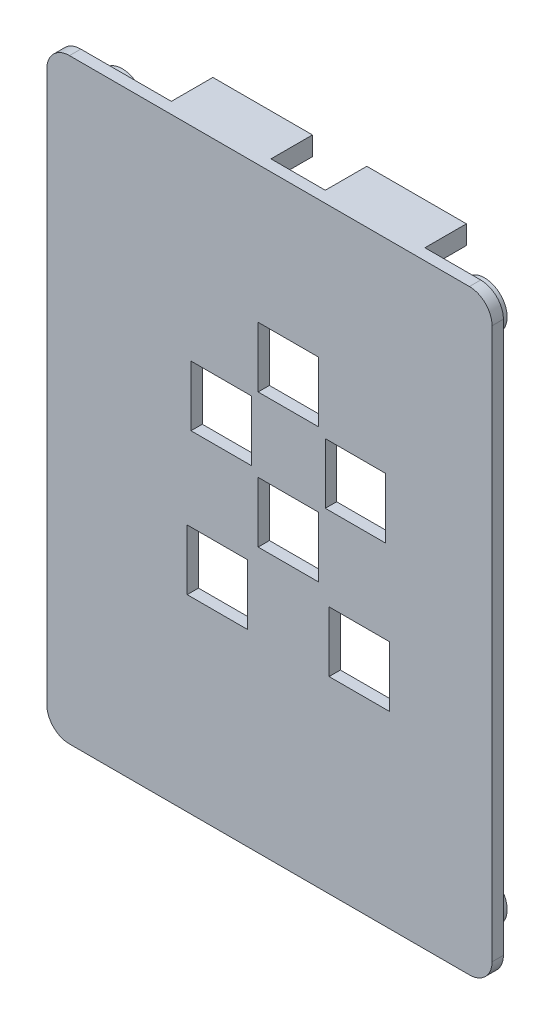
SolidWorks part; units mm, degrees
ref_plane "前视基准面" through (0, 0, 0) normal (0, 0, 1) x (1, 0, 0)
ref_plane "上视基准面" through (0, 0, 0) normal (0, 1, 0) x (1, 0, 0)
ref_plane "右视基准面" through (0, 0, 0) normal (1, 0, 0) x (0, 0, -1)
sketch "草图1" plane through (0, 0, 0) normal (0, 0, 1) x (1, 0, 0)
  line L0 (-23, 31.5) -> (23, 31.5) construction
  line L1 (-26.5, 39.5) -> (26.5, 39.5)
  line L2 (-29.5, 36.5) -> (-29.5, -36.5)
  line L3 (-26.5, -39.5) -> (26.5, -39.5)
  line L4 (29.5, 36.5) -> (29.5, -36.5)
  line L5 (-29.5, 39.5) -> (29.5, -39.5) construction
  line L6 (-29.5, -39.5) -> (29.5, 39.5) construction
  line L7 (-24, 37) -> (24, 37)
  line L8 (-27, 34) -> (-27, -34)
  line L9 (-24, -37) -> (24, -37)
  line L10 (27, 34) -> (27, -34)
  line L11 (-27, 37) -> (27, -37) construction
  line L12 (-27, -37) -> (27, 37) construction
  line L13 (23, 31.5) -> (23, -34.5) construction
  line L14 (23, -34.5) -> (-23, -34.5) construction
  line L15 (-23, -34.5) -> (-23, 31.5) construction
  line L16 (-29.5, 21) -> (-27, 21)
  line L17 (-29.5, 7) -> (-27, 7)
  line L18 (-29.5, 2) -> (-27, 2)
  line L19 (-29.5, -12) -> (-27, -12)
  line L20 (-14.5, 39.5) -> (-14.5, 37)
  line L21 (-1.3, 39.5) -> (-1.3, 37)
  line L22 (5.9, 39.5) -> (5.9, 37)
  line L23 (19.1, 39.5) -> (19.1, 37)
  line L24 (-21.7, -37) -> (-21.7, -39.5)
  line L25 (-0.1, -37) -> (-0.1, -39.5)
  line L26 (-27, 29.5) -> (-23, 29.5)
  line L27 (-21, 31.5) -> (-21, 37)
  line L28 (21, 37) -> (21, 31.5)
  line L29 (23, 29.5) -> (27, 29.5)
  line L30 (21, -34.5) -> (21, -37)
  line L31 (23, -32.5) -> (27, -32.5)
  line L32 (-27, -32.5) -> (-23, -32.5)
  line L33 (-21, -34.5) -> (-21, -37)
  line L34 (-8.7, -37) -> (-8.7, -39.5)
  line L35 (7.4, 12.5) -> (15.4, 12.5)
  line L36 (-1.5, 21.4) -> (6.5, 21.4)
  line L37 (-1.5, 21.4) -> (-1.5, 13.4)
  line L38 (-1.5, 13.4) -> (6.5, 13.4)
  line L39 (6.5, 21.4) -> (6.5, 13.4)
  line L40 (-1.5, 21.4) -> (6.5, 13.4) construction
  line L41 (-1.5, 13.4) -> (6.5, 21.4) construction
  line L42 (7.4, 12.5) -> (7.4, 4.5)
  line L43 (7.4, 4.5) -> (15.4, 4.5)
  line L44 (15.4, 12.5) -> (15.4, 4.5)
  line L45 (7.4, 12.5) -> (15.4, 4.5) construction
  line L46 (7.4, 4.5) -> (15.4, 12.5) construction
  line L47 (-10.4, 12.5) -> (-2.4, 12.5)
  line L48 (-10.4, 12.5) -> (-10.4, 4.5)
  line L49 (-10.4, 4.5) -> (-2.4, 4.5)
  line L50 (-2.4, 12.5) -> (-2.4, 4.5)
  line L51 (-10.4, 12.5) -> (-2.4, 4.5) construction
  line L52 (-10.4, 4.5) -> (-2.4, 12.5) construction
  line L53 (-1.5, 3.6) -> (6.5, 3.6)
  line L54 (-1.5, 3.6) -> (-1.5, -4.4)
  line L55 (-1.5, -4.4) -> (6.5, -4.4)
  line L56 (6.5, 3.6) -> (6.5, -4.4)
  line L57 (-1.5, 3.6) -> (6.5, -4.4) construction
  line L58 (-1.5, -4.4) -> (6.5, 3.6) construction
  line L59 (-10.9, -6.56) -> (-2.9, -6.56)
  line L60 (-10.9, -6.56) -> (-10.9, -14.56)
  line L61 (-10.9, -14.56) -> (-2.9, -14.56)
  line L62 (-2.9, -6.56) -> (-2.9, -14.56)
  line L63 (-10.9, -6.56) -> (-2.9, -14.56) construction
  line L64 (-10.9, -14.56) -> (-2.9, -6.56) construction
  line L65 (7.9, -6.56) -> (15.9, -6.56)
  line L66 (7.9, -6.56) -> (7.9, -14.56)
  line L67 (7.9, -14.56) -> (15.9, -14.56)
  line L68 (15.9, -6.56) -> (15.9, -14.56)
  line L69 (7.9, -6.56) -> (15.9, -14.56) construction
  line L70 (7.9, -14.56) -> (15.9, -6.56) construction
  line L71 (2.5, 8.5) -> (11.4, 8.5)
  line L72 (2.5, 17.4) -> (2.5, 8.5)
  line L73 (2.5, -10.56) -> (11.9, -10.56)
  line L74 (2.5, -0.4) -> (2.5, -10.56)
  line L75 (2.5, 8.5) -> (2.5, -0.4)
  line L76 (2.5, 8.5) -> (-6.4, 8.5)
  line L77 (2.5, -10.56) -> (-6.9, -10.56)
  line L78 (13.93, -4.21) -> (2.5, -4.21) construction
  line L79 (2.5, -4.21) -> (-8.93, -4.21) construction
  line L81 (2.5, 21.4) -> (2.5, 39.1991) construction
  circle A0 centre (-23, 31.5) radius 0.75
  circle A1 centre (23, 31.5) radius 0.75
  circle A2 centre (23, -34.5) radius 0.75
  circle A3 centre (-23, -34.5) radius 0.75
  arc A4 (-27, 34) -> (-24, 37) centre (-24, 34) cw
  arc A5 (24, 37) -> (27, 34) centre (24, 34) cw
  arc A6 (27, -34) -> (24, -37) centre (24, -34) cw
  arc A7 (-24, -37) -> (-27, -34) centre (-24, -34) cw
  arc A8 (-29.5, -36.5) -> (-26.5, -39.5) centre (-26.5, -36.5) ccw
  arc A9 (26.5, -39.5) -> (29.5, -36.5) centre (26.5, -36.5) ccw
  arc A10 (29.5, 36.5) -> (26.5, 39.5) centre (26.5, 36.5) ccw
  arc A11 (-29.5, 36.5) -> (-26.5, 39.5) centre (-26.5, 36.5) cw
  arc A12 (-23, 29.5) -> (-21, 31.5) centre (-23, 31.5) ccw
  arc A13 (21, 31.5) -> (23, 29.5) centre (23, 31.5) ccw
  arc A14 (21, -34.5) -> (23, -32.5) centre (23, -34.5) cw
  arc A15 (-21, -34.5) -> (-23, -32.5) centre (-23, -34.5) ccw
  circle A16 centre (24, 34) radius 3
  circle A17 centre (-24, 34) radius 3
  circle A18 centre (-24, -34) radius 3
  circle A19 centre (24, -34) radius 3
  circle A20 centre (2.5, 9.8) radius 2
  circle A21 centre (-8.93, -4.21) radius 2
  circle A22 centre (13.93, -4.21) radius 2
  circle A23 centre (2.5, -6.4449) radius 2
  point P0 (0, 0)
  point P5 (2.5, 17.4)
  point P6 (0, 0)
  point P11 (-23, 31.5)
  point P12 (23, 31.5)
  point P13 (23, -34.5)
  point P14 (-23, -34.5)
  point P98 (11.4, 8.5)
  point P103 (-6.4, 8.5)
  point P108 (2.5, -0.4)
  point P113 (-6.9, -10.56)
  point P118 (11.9, -10.56)
  point P130 (-6.4, 8.5)
  dimension "D7" = 1.5
  dimension "D22" = 3
  dimension "D25" = 2
  dimension "D28" = 2
  dimension "D30" = 2
  dimension "D31" = 2
  dimension "D34" = 2
  dimension "D41" = 4
  dimension "D3" = 2.5
  dimension "D4" = 2.5
  dimension "D5" = 46
  dimension "D6" = 66
  dimension "D8" = 4
  dimension "D9" = 4
  dimension "D10" = 2.5
  dimension "D11" = 5.5
  dimension "D12" = 14
  dimension "D13" = 14
  dimension "D14" = 5
  dimension "D15" = 10.5
  dimension "D16" = 13.2
  dimension "D17" = 13.2
  dimension "D18" = 7.2
  dimension "D19" = 3.9
  dimension "D20" = 21.6
  dimension "D21" = 1.3
  dimension "D23" = 2
  dimension "D24" = 2
  dimension "D26" = 2
  dimension "D27" = 2
  dimension "D29" = 2
  dimension "D32" = 2
  dimension "D33" = 2
  dimension "D35" = 54
  dimension "D36" = 68
  dimension "D37" = 13
  dimension "D38" = 8
  dimension "D39" = 8.9
  dimension "D40" = 10.16
  dimension "D42" = 1.3
  dimension "D43" = 4.1151
  dimension "D44" = 11.43
  dimension "D45" = 6.35
  dimension "D46" = 20.5
  dimension "D47" = 10.1
  dimension "D48" = 9.4
extrude "凸台-拉伸1" add sketch "草图1" along normal blind 1.5 contours L50 L47 L48 L49 | L39 L36 L37 L38 | L44 L35 L42 L43 | L68 L65 L66 L67 | L62 L59 L60 L61 | L53 L75 L74 L55 L56 | L75 L53 L54 L55 L74 | L4 A9 L3 A8 L2 A11 L1 A10 region at (8.0131, -8.56, 0) region at (-3.0131, -12.56, 0) region at (4.5, -0.4, 0) region at (0.5, -0.4, 0) region at (-2.5131, 6.5, 0) region at (0.5, 13.5131, 0) region at (11.4, 12.3869, 0)
extrude "凸台-拉伸2" add sketch "草图1<10>" against normal blind 8.5 contours L2 L17 L8 L16 | L2 L19 L8 L18 region at (-28.25, 14, 0) region at (-28.25, -5, 0)
sketch "草图1<10>" plane through (0, 0, 0) normal (0, 0, 1) x (1, 0, 0) same geometry as "草图1"
extrude "凸台-拉伸3" add sketch "草图1<11>" against normal blind 5.5 contours L23 L1 L22 L7 | L21 L1 L20 L7 | L34 L9 L24 L3 region at (-7.9, 38.25, 0) region at (12.5, 38.25, 0) region at (-15.2, -38.25, 0)
sketch "草图1<11>" plane through (0, 0, 0) normal (0, 0, 1) x (1, 0, 0) same geometry as "草图1"
extrude "凸台-拉伸4" add sketch "草图1<13>" against normal blind 3 contours A18 | A19 | A16 | A17
sketch "草图1<13>" plane through (0, 0, 0) normal (0, 0, 1) x (1, 0, 0) same geometry as "草图1"
extrude "凸台-拉伸5" add sketch "草图1<14>" against normal blind 1 contours L9 L34 L3 L25 region at (-4.4, -38.25, 0)
sketch "草图1<14>" plane through (0, 0, 0) normal (0, 0, 1) x (1, 0, 0) same geometry as "草图1"
extrude "切除-拉伸1" cut sketch "草图1<15>" along normal blind 1.4 contours A20 | A21 | A23 | A22
sketch "草图1<15>" plane through (0, 0, 0) normal (0, 0, 1) x (1, 0, 0) same geometry as "草图1"
